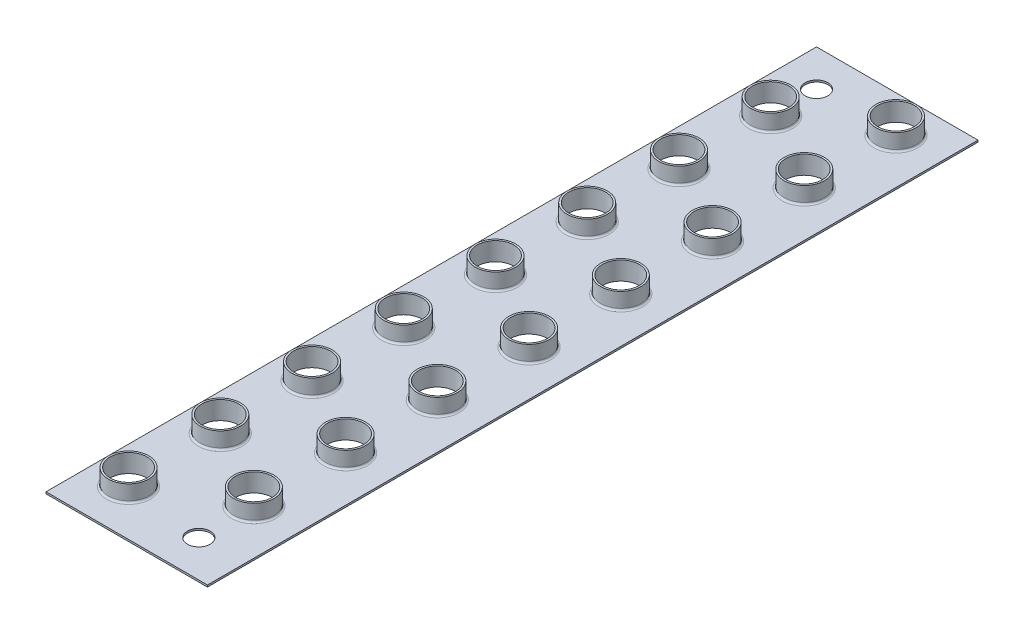
SolidWorks part; units mm, degrees
ref_plane "Front Plane" through (0, 0, 0) normal (0, 0, 1) x (1, 0, 0)
ref_plane "Top Plane" through (0, 0, 0) normal (0, 1, 0) x (1, 0, 0)
ref_plane "Right Plane" through (0, 0, 0) normal (1, 0, 0) x (0, 0, -1)
sketch "Sketch1" plane through (0, 0, 0) normal (0, 1, 0) x (1, 0, 0)
  line L1 (0, 0) -> (44, 0)
  line L2 (0, 0) -> (0, -210)
  line L3 (0, -210) -> (44, -210)
  line L4 (44, 0) -> (44, -210)
  dimension "D1" = 44
  dimension "D2" = 210
extrude "Boss-Extrude1" add sketch "Sketch1" along normal blind 0.5
sketch "Sketch2" plane through (0, 0.5, 0) normal (0, 1, 0) x (1, 0, 0)
  line L0 (44, 0) -> (0, 0) construction
  line L2 (0, 0) -> (0, -210) construction
  line L3 (31.6506, -10) -> (44, -10) construction
  line L4 (44, -210) -> (44, 0) construction
  line L5 (10, -22.5) -> (0, -22.5) construction
  circle A0 centre (31.6506, -10) radius 5.5
  circle A1 centre (10, -22.5) radius 5.5
  circle A16 centre (31.6506, -10) radius 5
  circle A17 centre (10, -22.5) radius 5
  circle A18 centre (10, -47.5) radius 5
  circle A19 centre (10, -47.5) radius 5.5
  circle A20 centre (31.6506, -35) radius 5.5
  circle A21 centre (31.6506, -35) radius 5
  circle A22 centre (10, -72.5) radius 5
  circle A23 centre (10, -72.5) radius 5.5
  circle A24 centre (31.6506, -60) radius 5.5
  circle A25 centre (31.6506, -60) radius 5
  circle A26 centre (10, -97.5) radius 5
  circle A27 centre (10, -97.5) radius 5.5
  circle A28 centre (31.6506, -85) radius 5.5
  circle A29 centre (31.6506, -85) radius 5
  circle A30 centre (10, -122.5) radius 5
  circle A31 centre (10, -122.5) radius 5.5
  circle A32 centre (31.6506, -110) radius 5.5
  circle A33 centre (31.6506, -110) radius 5
  circle A34 centre (10, -147.5) radius 5
  circle A35 centre (10, -147.5) radius 5.5
  circle A36 centre (31.6506, -135) radius 5.5
  circle A37 centre (31.6506, -135) radius 5
  circle A38 centre (10, -172.5) radius 5
  circle A39 centre (10, -172.5) radius 5.5
  circle A40 centre (31.6506, -160) radius 5.5
  circle A41 centre (31.6506, -160) radius 5
  circle A42 centre (10, -197.5) radius 5
  circle A43 centre (10, -197.5) radius 5.5
  circle A44 centre (31.6506, -185) radius 5.5
  circle A45 centre (31.6506, -185) radius 5
  dimension "D1" = 10
  dimension "D4" = 10
  dimension "D6" = 8
  dimension "D8" = 0.5
  dimension "D9" = 0.5
  dimension "D7" = 10
  dimension "D2" = 10
  dimension "D3" = 25
  dimension "D5" = 22.5
extrude "Boss-Extrude2" add sketch "Sketch2" along normal blind 4.5
fillet "Fillet1" radius 0.5 16 edges at (10, 0.5, 28) (10, 0.5, 53) (10, 0.5, 78) (10, 0.5, 103) (10, 0.5, 128) (10, 0.5, 153) (10, 0.5, 178) (10, 0.5, 203) (31.6506, 0.5, 190.5) (31.6506, 0.5, 165.5) (31.6506, 0.5, 140.5) (31.6506, 0.5, 115.5) (31.6506, 0.5, 90.5) (31.6506, 0.5, 65.5) (31.6506, 0.5, 40.5) (31.6506, 0.5, 15.5)
sketch "Sketch3" plane through (0, 0.5, 0) normal (0, 1, 0) x (1, 0, 0)
  line L0 (44, 0) -> (0, 0) construction
  line L1 (10, -22.5) -> (10, 0) construction
  line L2 (31.6506, -10) -> (31.6506, -22.5) construction
  line L3 (0, -210) -> (44, -210) construction
  circle A0 centre (10, -10) radius 3.1
  circle A1 centre (31.6506, -200) radius 3.1
  dimension "D1" = 6.2
  dimension "D3" = 10
  dimension "D2" = 10
extrude "Cut-Extrude1" cut sketch "Sketch3" against normal blind 4.5
extrude "Cut-Extrude2" cut sketch "Sketch2<2>" against normal blind 10 contours A16 | A17 region at (31.6506, 0.5, 10) region at (10, 0.5, 22.5)
sketch "Sketch2<2>" plane through (0, 0.5, 0) normal (0, 1, 0) x (1, 0, 0) same geometry as "Sketch2"
pattern_linear "LPattern1" count 8 spacing 25 along (0, 0, 1) of "Cut-Extrude2"
